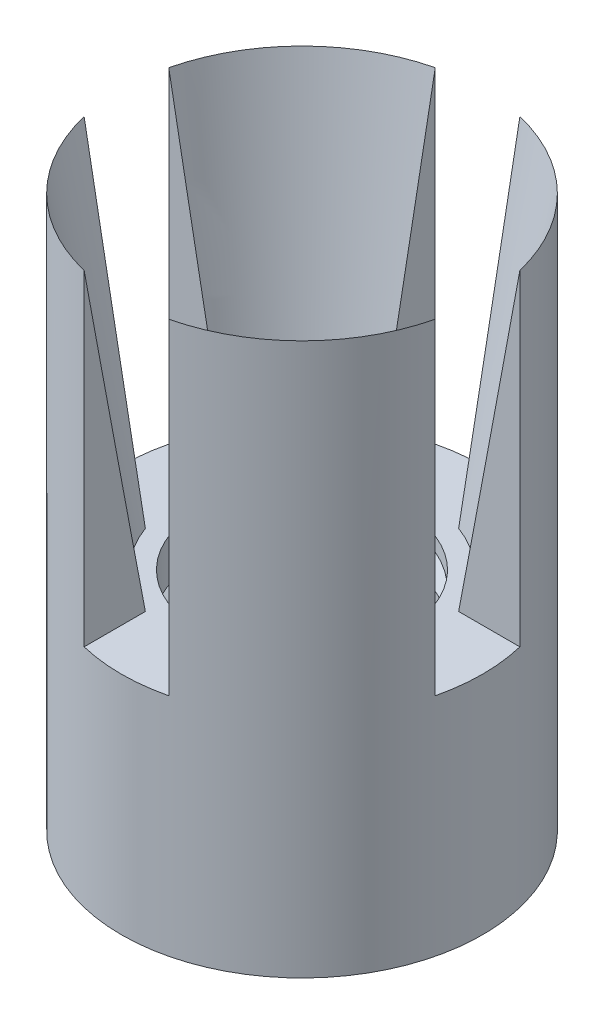
SolidWorks part; units mm, degrees
ref_plane "Front Plane" through (0, 0, 0) normal (0, 0, 1) x (1, 0, 0)
ref_plane "Top Plane" through (0, 0, 0) normal (0, 1, 0) x (1, 0, 0)
ref_plane "Right Plane" through (0, 0, 0) normal (1, 0, 0) x (0, 0, -1)
sketch "Sketch1" plane through (0, 0, 0) normal (0, 1, 0) x (1, 0, 0)
  circle A0 centre (0, 0) radius 2.8956
  circle A1 centre (0, 0) radius 5.08
  dimension "D1" = 5.7912
  dimension "D2" = 10.16
extrude "Boss-Extrude1" add sketch "Sketch1" along normal blind 6.35 contours A1 A0 region at (-4.9363, 0, 0)
sketch "Sketch2" plane through (0, 6.35, 0) normal (0, 1, 0) x (1, 0, 0)
  circle A0 centre (0, 0) radius 5.08
  dimension "D1" = 10.16
extrude "Boss-Extrude2" add sketch "Sketch2" along normal blind 12.7
ref_plane "Plane1" through (0, 6.35, 0) normal (0, 1, 0) x (1, 0, 0)
ref_axis "Axis1" through (0, 19.05, 0) along (0, -1, 0)
sketch "Sketch6" plane through (0, 0, 0) normal (0, 0, 1) x (1, 0, 0)
  line L0 (-5.08, 19.05) -> (5.08, 19.05) construction
  line L1 (0, 19.05) -> (-5.715, 19.05)
  line L2 (-5.715, 19.05) -> (-3.1775, 6.35)
  line L3 (5.588, 6.35) -> (-5.588, 6.35) construction
  line L4 (-3.1775, 6.35) -> (-5.715, 6.35)
  line L5 (-5.715, 6.35) -> (-5.715, 19.05)
  line L6 (0, 19.05) -> (0, 0) construction
  dimension "D1" = 3.1775
  dimension "D2" = 5.715
extrude "Cut-Extrude2" cut sketch "Sketch6" against normal mid plane 2.3812 contours L5 L4 L2 region at (-4.8692, 10.5833, 0)
sketch "Sketch3" plane through (0, 6.35, 0) normal (0, 1, 0) x (1, 0, 0)
  circle A0 centre (0, 0) radius 3.429
  dimension "D1" = 6.858
sketch "Sketch4" plane through (0, 19.05, 0) normal (0, 1, 0) x (1, 0, 0)
  circle A0 centre (0, 0) radius 5.715
  dimension "D1" = 11.43
loft "Cut-Loft2" cut profiles "Sketch3", "Sketch4" connector at (0, 6.35, 3.429) connector at (0, 19.05, 5.715)
sketch "Sketch8" plane through (0, 0, 0) normal (1, 0, 0) x (0, 0, -1)
  line L0 (0, 0) -> (0, 24.7529) construction
  line L1 (0, 19.05) -> (0, 0) construction
  line L2 (5.588, 6.35) -> (-5.588, 6.35) construction
  line L3 (-1.1906, 6.35) -> (1.1906, 6.35)
  line L4 (-1.1906, 6.35) -> (-1.1906, 23.7829)
  line L5 (-1.1906, 23.7829) -> (1.1906, 23.7829)
  line L6 (1.1906, 6.35) -> (1.1906, 23.7829)
  line L7 (-1.1906, 6.35) -> (1.1906, 23.7829) construction
  line L8 (-1.1906, 23.7829) -> (1.1906, 6.35) construction
  point P9 (0, 15.0665)
  point P12 (0, 23.7829)
  dimension "D1" = 2.3812
extrude "Cut-Extrude4" cut sketch "Sketch8" against normal through all both and the other way through all
sketch "Sketch9" plane through (0, 0, 0) normal (0, 0, 1) x (1, 0, 0)
  line L0 (0, 0) -> (0, 25.1481) construction
  line L1 (0, 19.05) -> (0, 0) construction
  line L2 (5.588, 6.35) -> (-5.588, 6.35) construction
  line L3 (-1.1906, 6.35) -> (1.1906, 6.35)
  line L4 (-1.1906, 6.35) -> (-1.1906, 24.1062)
  line L5 (-1.1906, 24.1062) -> (1.1906, 24.1062)
  line L6 (1.1906, 6.35) -> (1.1906, 24.1062)
  line L7 (-1.1906, 6.35) -> (1.1906, 24.1062) construction
  line L8 (-1.1906, 24.1062) -> (1.1906, 6.35) construction
  point P9 (0, 15.2281)
  point P12 (0, 24.1062)
  dimension "D1" = 2.3812
extrude "Cut-Extrude5" cut sketch "Sketch9" against normal through all both and the other way through all
thread "Thread1" pitch 1.27 method cut profile "Thread Profile1" start angle 0, offset 0, length 0, pitch 1.27, diameter 5.7912
ref_plane "Plane2" through (-2.8956, 6.35, 0) normal (0, 0, 1) x (-1, 0, 0)
sketch "Thread Profile1" plane through (-2.8956, 6.35, 0) normal (0, 0, 1) x (-1, 0, 0)
  line L0 (0, 0) -> (0, 1.27) construction
  line L1 (0, 0) -> (0.6874, 0.3969)
  line L2 (0.6874, 0.3969) -> (0.6874, 0.5556)
  line L3 (0.6874, 0.5556) -> (0, 0.9525)
  line L4 (0.6874, 0.4762) -> (0, 0.4762) construction
  line L11 (0, 0) -> (0, 0.9525)
  point P2 (0, 0)
  dimension "Pitch" = 1.27
  dimension "Profile_Angle" = 60
  dimension "Profile_Land" = 0.1588
  dimension "Profile_Height" = 0.6874
